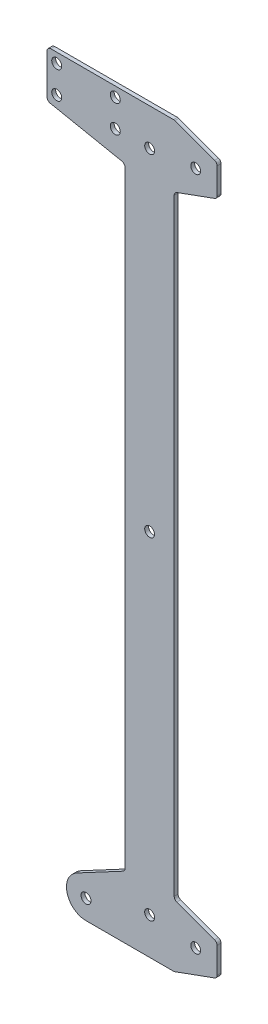
SolidWorks part; units mm, degrees
ref_plane "Front Plane" through (0, 0, 0) normal (0, 0, 1) x (1, 0, 0)
ref_plane "Top Plane" through (0, 0, 0) normal (0, 1, 0) x (1, 0, 0)
ref_plane "Right Plane" through (0, 0, 0) normal (1, 0, 0) x (0, 0, -1)
sketch "Sketch1" plane through (0, 0, 0) normal (0, 0, 1) x (1, 0, 0)
  line L1 (-10, 150) -> (10, 150)
  line L2 (-10, 150) -> (-10, -150)
  line L3 (-10, -150) -> (10, -150)
  line L4 (10, 150) -> (10, -150)
  line L5 (-10, 150) -> (10, -150) construction
  line L6 (-10, -150) -> (10, 150) construction
  point P0 (0, 0)
  dimension "D1" = 300
  dimension "20mm" = 20
extrude "Boss-Extrude1" add sketch "Sketch1" along normal blind 1.5875
sketch "Sketch2" plane through (0, 0, 1.5875) normal (0, 0, 1) x (1, 0, 0)
  line L0 (10, 150) -> (27.4625, 143.65)
  line L1 (27.4625, 143.65) -> (27.4625, 130.95)
  line L2 (27.4625, 130.95) -> (10, 124.6)
  line L3 (10, -150) -> (10, 150) construction
  line L4 (10, 124.6) -> (10, 150)
  line L5 (10, 150) -> (-10, 150) construction
  line L6 (-10, 0) -> (10, 0) construction
  line L7 (-10, 150) -> (-10, -150) construction
  line L8 (10, -124.6) -> (10, -150)
  line L9 (27.4625, -130.95) -> (10, -124.6)
  line L10 (27.4625, -143.65) -> (27.4625, -130.95)
  line L11 (10, -150) -> (27.4625, -143.65)
  line L12 (18.7312, 140.475) -> (18.7312, 134.125) construction
  circle A1 centre (18.7312, 134.125) radius 5 construction
  circle A2 centre (18.7312, 140.475) radius 2 construction
  circle A4 centre (18.7312, -134.125) radius 5 construction
  circle A5 centre (18.7312, -134.125) radius 2 construction
  circle A6 centre (18.7312, 137.3) radius 2
  circle A7 centre (18.7312, -137.3) radius 2
  point P3 (27.4625, 137.3)
  point P8 (10, 137.3)
  point P13 (18.7312, 127.775)
  point P31 (27.4625, -137.3)
  dimension "D3" = 4
  dimension "D4" = 10
  dimension "D1" = 17.4625
  dimension "2.5" = 25.4
  dimension "D2" = 12.7
  dimension "D5" = 9.525
  dimension "D6" = 9.525
extrude "Boss-Extrude2" add sketch "Sketch2" against normal up to surface (1.5875 mm away) up to face at (0, 0, 0)
sketch "Sketch4" plane through (0, 0, 1.5875) normal (0, 0, 1) x (1, 0, 0)
  line L0 (0, 150) -> (0, 135) construction
  line L2 (0, 135) -> (0, 0) construction
  line L3 (0, 0) -> (0, -135) construction
  line L4 (0, -135) -> (0, -150) construction
  line L6 (10, 150) -> (-10, 150) construction
  line L7 (-10, -150) -> (10, -150) construction
  circle A0 centre (0, -135) radius 2
  circle A1 centre (0, 0) radius 2
  circle A2 centre (0, 135) radius 2
  dimension "D4" = 4
  dimension "D1" = 15
  dimension "D2" = 135
  dimension "D3" = 135
extrude "Cut-Extrude1" cut sketch "Sketch4" against normal through all
sketch "Sketch5" plane through (0, 0, 1.5875) normal (0, 0, 1) x (1, 0, 0)
  line L0 (-10, 124.6) -> (-41.75, 130.95)
  line L1 (-10, 150) -> (-10, -150) construction
  line L2 (-41.75, 130.95) -> (-41.75, 150)
  line L3 (-41.75, 150) -> (-10, 150)
  line L4 (-10, 150) -> (-10, 124.6)
  line L5 (10, 150) -> (-10, 150) construction
  line L6 (-41.75, 146.0313) -> (-37.7813, 146.0313) construction
  line L7 (-13.9688, 146.0313) -> (-10, 146.0313) construction
  line L8 (-10, -150) -> (-25.875, -150)
  line L9 (-29.6103, -135.0588) -> (-10, -124.6)
  line L10 (-10, -124.6) -> (-10, -150)
  circle A0 centre (-13.9688, 146.0313) radius 2.032
  circle A1 centre (-13.9688, 134.9188) radius 2.032
  circle A2 centre (-37.7813, 146.0313) radius 2.032
  circle A3 centre (-37.7813, 134.9188) radius 2.032
  arc A4 (-25.875, -150) -> (-29.6103, -135.0588) centre (-25.875, -142.0625) cw
  circle A5 centre (-25.875, -142.0625) radius 2.032
  point P24 (-25.875, 150)
  dimension "D5" = 4.064
  dimension "D9" = 4.064
  dimension "D10" = 7.9375
  dimension "D1" = 0
  dimension "D2" = 19.05
  dimension "D3" = 25.4
  dimension "D4" = 31.75
  dimension "D6" = 11.1125
  dimension "D7" = 23.8125
  dimension "D8" = 3.9688
  dimension "D11" = 25.4
extrude "Boss-Extrude3" add sketch "Sketch5" against normal up to surface (1.5875 mm away) up to face at (2, -135, 0)
fillet "Fillet3" radius 1.5875 11 edges at (-10, -124.6, 0.7937) (27.4625, -143.65, 0.7937) (27.4625, -130.95, 0.7937) (10, -124.6, 0.7937) (27.4625, 130.95, 0.7937) (10, 124.6, 0.7937) (27.4625, 143.65, 0.7937) (10, 150, 0.7937) (-10, 124.6, 0.7937) (-41.75, 130.95, 0.7937) (-41.75, 150, 0.7937)
sketch "Sketch6" [suppressed] plane through (0, 0, 3.175) normal (0, 0, 1) x (1, 0, 0)
  line L0 (-10, -124.6) -> (-10, -150) construction
  line L1 (-10, -150) -> (-25.875, -150) construction
  line L2 (-29.6103, -135.0588) -> (-10, -124.6) construction
  line L3 (-10, -124.6) -> (-10, -150)
  line L4 (-10, -150) -> (-25.875, -150)
  line L5 (-29.6103, -135.0588) -> (-10, -124.6)
  circle A0 centre (-25.875, -142.0625) radius 2.032 construction
  arc A1 (-29.6103, -135.0588) -> (-25.875, -150) centre (-25.875, -142.0625) ccw construction
  circle A2 centre (-25.875, -142.0625) radius 2.032
  arc A3 (-29.6103, -135.0588) -> (-25.875, -150) centre (-25.875, -142.0625) ccw
extrude "Boss-Extrude4" [suppressed] add sketch "Sketch6" against normal up to vertex up to point (-10, -123.6475, 0)
fillet "Fillet4" [suppressed] radius 0.7937
fillet "Fillet5" [suppressed] radius 1.5875
sketch "Sketch7" [suppressed] plane through (0, 0, 0) normal (0, 0, -1) x (-1, 0, 0)
  line L0 (-26.94, 143.84) -> (-65.04, 129.9855)
  line L1 (-65.5625, 129.2395) -> (-65.5625, 24.4645)
  line L2 (-64.9742, 23.6978) -> (-10, 8.9675)
  line L3 (-10, 150) -> (-26.94, 143.84) construction
  line L4 (-10, 8.9675) -> (-10, 124.044)
  line L5 (-27.4625, 143.094) -> (-27.4625, 131.506) construction
  line L6 (-26.94, 130.76) -> (-10.5225, 124.79) construction
  line L7 (-27.4625, 143.094) -> (-27.4625, 131.506)
  line L8 (-26.94, 130.76) -> (-10.5225, 124.79)
  line L10 (-10, 150) -> (9.2063, 150) construction
  line L11 (-48.989, 57.925) -> (-48.989, 61.1) construction
  line L12 (-38.6703, 35.7) -> (-59.3078, 35.7) construction
  line L13 (-38.6703, 35.7) -> (-38.6703, 80.15) construction
  line L14 (-38.6703, 80.15) -> (-59.3078, 80.15) construction
  line L15 (-59.3078, 35.7) -> (-59.3078, 80.15) construction
  line L16 (-38.6703, 35.7) -> (-59.3078, 80.15) construction
  line L17 (-38.6703, 80.15) -> (-59.3078, 35.7) construction
  line L18 (-48.989, 111.9) -> (-48.989, 61.1) construction
  line L19 (-10, -124.044) -> (-10, 124.044) construction
  arc A0 (-65.04, 129.9855) -> (-65.5625, 129.2395) centre (-64.7687, 129.2395) ccw
  arc A1 (-65.5625, 24.4645) -> (-64.9742, 23.6978) centre (-64.7687, 24.4645) ccw
  arc A2 (-26.94, 143.84) -> (-27.4625, 143.094) centre (-26.6688, 143.094) ccw construction
  arc A3 (-27.4625, 131.506) -> (-26.94, 130.76) centre (-26.6688, 131.506) ccw construction
  arc A4 (-10, 124.044) -> (-10.5225, 124.79) centre (-10.7937, 124.044) ccw construction
  arc A5 (-26.94, 143.84) -> (-27.4625, 143.094) centre (-26.6688, 143.094) ccw
  arc A6 (-27.4625, 131.506) -> (-26.94, 130.76) centre (-26.6688, 131.506) ccw
  arc A7 (-10, 124.044) -> (-10.5225, 124.79) centre (-10.7937, 124.044) ccw
  arc A8 (10, 149.2063) -> (9.2063, 150) centre (9.2063, 149.2063) ccw construction
  circle A9 centre (-48.989, 111.9) radius 4.7625
  circle A10 centre (-48.989, 61.1) radius 6.985
  circle A11 centre (-59.3078, 80.15) radius 2.032
  circle A12 centre (-59.3078, 35.7) radius 2.032
  circle A13 centre (-38.6703, 35.7) radius 2.032
  circle A14 centre (-38.6703, 80.15) radius 2.032
  point P32 (-48.989, 57.925)
  dimension "D4" = 9.525
  dimension "D6" = 13.97
  dimension "D11" = 4.064
  dimension "D1" = 38.1
  dimension "D2" = 120.65
  dimension "D3" = 16.5735
  dimension "D5" = 50.8
  dimension "D7" = 3.175
  dimension "D8" = 44.45
  dimension "D9" = 50.8
  dimension "D10" = 20.6375
  dimension "D12" = 75
extrude "Boss-Extrude5" [suppressed] add sketch "Sketch7" against normal up to surface (3.175 mm away) up to face at (2, -135, 1.5875)
sketch "Sketch8" [suppressed] plane through (0, 0, 3.175) normal (0, 0, 1) x (1, 0, 0)
  line L0 (48.989, 61.1) -> (48.989, 80.15) construction
  line L1 (48.989, 61.1) -> (29.939, 61.1) construction
  line L2 (48.989, 61.1) -> (48.989, 42.05) construction
  line L3 (48.989, 111.9) -> (48.989, 121.425) construction
  line L4 (48.989, 111.9) -> (48.989, 102.375) construction
  line L5 (19.6203, 80.15) -> (19.6203, 67.45) construction
  circle A0 centre (48.989, 80.15) radius 2.032
  circle A1 centre (29.939, 61.1) radius 2.032
  circle A2 centre (48.989, 42.05) radius 2.032
  circle A3 centre (59.3078, 80.15) radius 2.032 construction
  circle A4 centre (48.989, 121.425) radius 2.032
  circle A5 centre (48.989, 102.375) radius 2.032
  circle A6 centre (19.6203, 67.45) radius 2.032
  circle A7 centre (19.6203, 80.15) radius 2.032
  dimension "D2" = 9.525
  dimension "D1" = 19.05
  dimension "D3" = 12.7
  dimension "D4" = 6.35
  dimension "D5" = 10.3187
extrude "Cut-Extrude2" [suppressed] cut sketch "Sketch8" against normal through all
